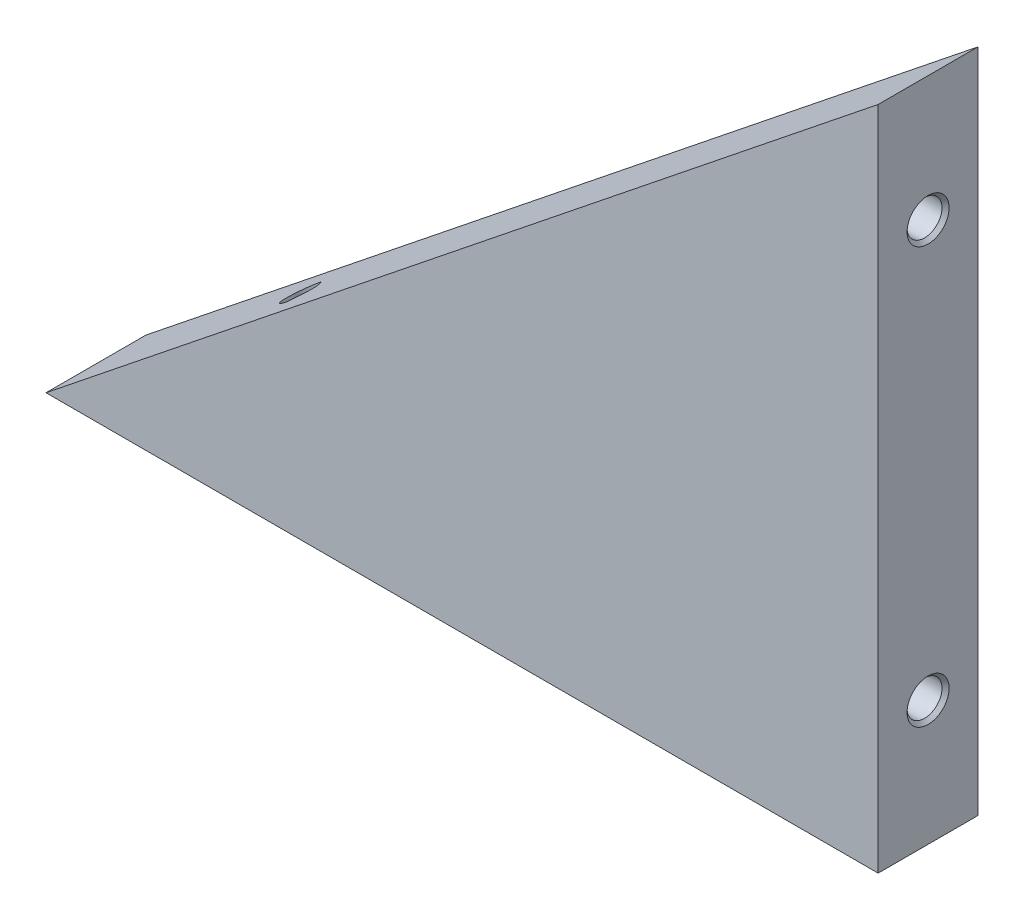
SolidWorks part; units mm, degrees
ref_plane "Vorne" through (0, 0, 0) normal (0, 0, 1) x (1, 0, 0)
ref_plane "Oben" through (0, 0, 0) normal (0, 1, 0) x (1, 0, 0)
ref_plane "Rechts" through (0, 0, 0) normal (1, 0, 0) x (0, 0, -1)
ref_plane "E_Boden" through (0, 1, 0) normal (0, 1, 0) x (1, 0, 0)
sketch "Skizze1" plane through (0, 0, 0) normal (0, 0, 1) x (1, 0, 0)
  line L0 (0, 10) -> (0, -9.5229) construction
  line L1 (-15.5467, 0) -> (14.4334, 0) construction
  line L2 (100, 0) -> (100, 80)
  line L3 (100, 80) -> (0, 0)
  line L4 (0, 0) -> (100, 0)
  dimension "D1" = 80
  dimension "D2" = 100
extrude "Aufsatz-Linear austragen1" add sketch "Skizze1" along normal blind 12
hole_wizard "M5 Gewindebohrung2" positions "Skizze7" profile "Skizze8" tap size "M5" standard "DIN"
sketch "Skizze7" plane through (100, 0, 0) normal (1, 0, 0) x (0, 0, -1)
  line L2 (-6, 80) -> (-6, 0) construction
  line L3 (-12, 80) -> (0, 80) construction
  line L4 (-12, 0) -> (0, 0) construction
  line L6 (-12, 40) -> (0, 40) construction
  line L7 (-12, 0) -> (-12, 80) construction
  line L8 (0, 0) -> (0, 80) construction
  point P0 (-6, 65)
  point P2 (-6, 15)
  dimension "D1" = 50
sketch "Skizze8" plane through (100, 65, 6) normal (0, 1, 0) x (0, 0, -1)
  line L0 (0, 0) -> (0, 16.2618)
  line L1 (0, 16.2618) -> (2.1, 15)
  line L2 (2.1, 15) -> (2.1, 0.425)
  line L3 (2.1, 0.425) -> (2.525, 0)
  line L5 (2.525, 0) -> (0, 0)
  line L6 (-2.1, 0.425) -> (-2.525, 0) construction
  line L10 (0, 16.2618) -> (-2.1, 15) construction
  line L11 (0, -6.35) -> (0, 107.95) construction
  dimension "Bohrerdurchmesser" = 4.2
  dimension "Bohrungstiefe" = 15
  dimension "Senkdurchmesser (Oben)" = 5.05
  dimension "Senkwinkel (Oben)" = 90
  dimension "Spitzenwinkel" = 118
cosmetic thread "Bohrungsgewinde3" parameters "D1"=10, "D2"=5
cosmetic thread "Bohrungsgewinde4" parameters "D1"=10, "D2"=5
hole_wizard "M5 Gewindebohrung3" positions "Skizze9" profile "Skizze10" tap size "M5" standard "DIN"
sketch "Skizze9" plane through (0, 0, 0) normal (0, -1, 0) x (-1, 0, 0)
  line L0 (-100, -6) -> (0, -6) construction
  line L1 (-100, -12) -> (-100, 0) construction
  line L2 (0, -12) -> (0, 0) construction
  line L4 (-50, 0) -> (-50, -12) construction
  line L5 (0, 0) -> (-100, 0) construction
  line L6 (0, -12) -> (-100, -12) construction
  point P0 (-25, -6)
  point P2 (-75, -6)
  dimension "D1" = 50
sketch "Skizze10" plane through (25, 0, 6) normal (1, 0, 0) x (0, 0, -1)
  line L0 (0, 0) -> (0, 21.2618)
  line L1 (0, 21.2618) -> (2.1, 20)
  line L2 (2.1, 20) -> (2.1, 0.425)
  line L3 (2.1, 0.425) -> (2.525, 0)
  line L5 (2.525, 0) -> (0, 0)
  line L6 (-2.1, 0.425) -> (-2.525, 0) construction
  line L10 (0, 21.2618) -> (-2.1, 20) construction
  line L11 (0, -6.35) -> (0, 107.95) construction
  dimension "Bohrerdurchmesser" = 4.2
  dimension "Bohrungstiefe" = 20
  dimension "Senkdurchmesser (Oben)" = 5.05
  dimension "Senkwinkel (Oben)" = 90
  dimension "Spitzenwinkel" = 118
cosmetic thread "Bohrungsgewinde5" parameters "D1"=10, "D2"=5
cosmetic thread "Bohrungsgewinde6" parameters "D1"=10, "D2"=5
